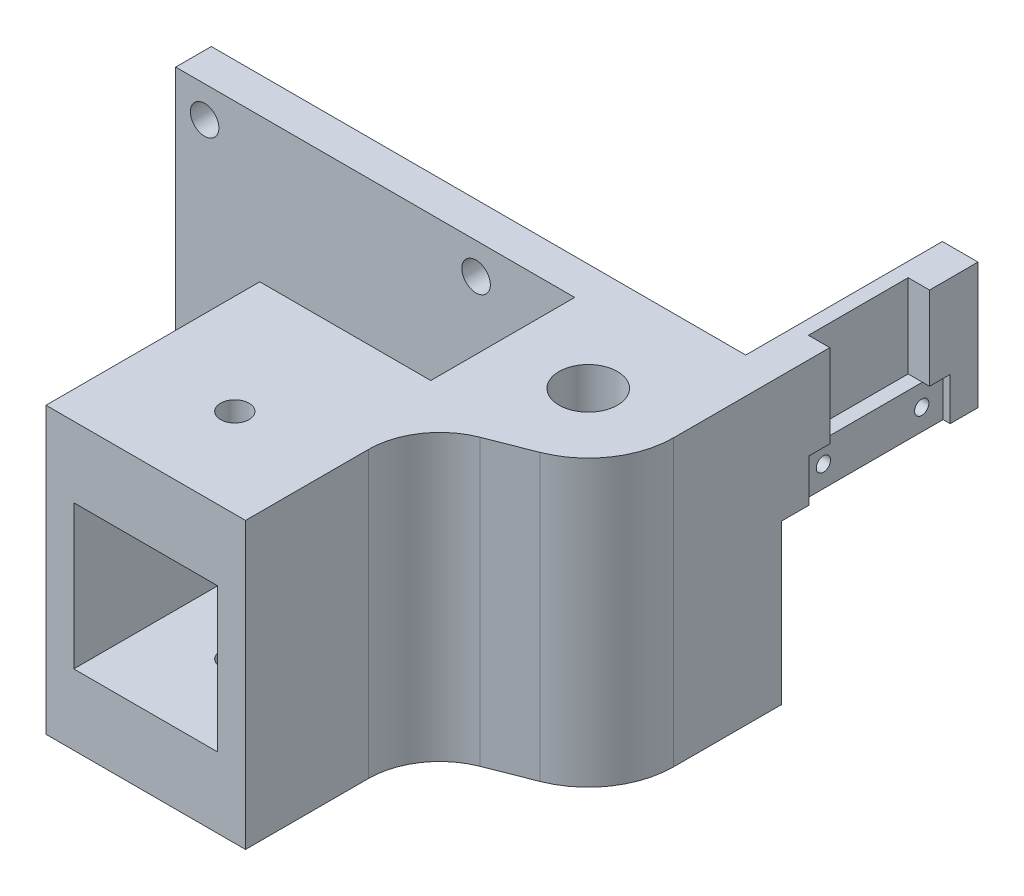
SolidWorks part; units mm, degrees
ref_plane "Front Plane" through (0, 0, 0) normal (0, 0, 1) x (1, 0, 0)
ref_plane "Top Plane" through (0, 0, 0) normal (0, 1, 0) x (1, 0, 0)
ref_plane "Right Plane" through (0, 0, 0) normal (1, 0, 0) x (0, 0, -1)
sketch "Sketch1" plane through (0, 0, 0) normal (0, 1, 0) x (1, 0, 0)
  line L0 (-32, 55.2) -> (-32, 50.2)
  line L1 (-32, 50.2) -> (24, 50.2)
  line L2 (24, 50.2) -> (24, 30)
  line L3 (24, 30) -> (0, 30)
  line L4 (0, 30) -> (0, 0)
  line L5 (0, 0) -> (28, 0)
  line L6 (28, 0) -> (28, 17.2586)
  line L7 (28, 55.2) -> (-32, 55.2)
  line L9 (40.3722, 28.9249) -> (34.3565, 26.5712)
  line L10 (28, 55.2) -> (43, 55.2)
  line L11 (43, 55.2) -> (43, 82.8)
  line L12 (43, 82.8) -> (48, 82.8)
  line L13 (48, 82.8) -> (48, 40.1)
  circle A1 centre (36, 40.1) radius 4.1
  arc A2 (48, 40.1) -> (40.3722, 28.9249) centre (36, 40.1) cw
  arc A3 (28, 17.2586) -> (34.3565, 26.5712) centre (38, 17.2586) cw
  point P8 (48, 51.7368)
  point P10 (47.3197, 55.2)
  point P11 (28, 12.7689)
  point P12 (48, 37.2626)
  point P18 (24, 40.1)
  point P19 (43.0102, 41.2257)
  point P22 (45.4925, 30.8582)
  point P23 (48, 30.8582)
  point P24 (0, 0)
  point P25 (28, 20.2156)
  point P26 (48, 34.6255)
  point P29 (38, 40.1)
  point P30 (37.365, 40.1)
  point P31 (0, 0)
  point P32 (28, 20.5347)
  point P33 (28, 24.0843)
  point P36 (43, 69)
  dimension "D6" = 8.2
  dimension "D7" = 5
  dimension "D10" = 10
  dimension "D1" = 5
  dimension "D2" = 4
  dimension "D3" = 30
  dimension "D4" = 20.2
  dimension "D5" = 28
  dimension "D8" = 8
  dimension "D9" = 19
  dimension "D11" = 13.8
extrude "Boss-Extrude1" add sketch "Sketch1" along normal blind 40 contours L6 A1 L9 | L6 L7 L0 L1 L2 L3 L4 L5 region at (-2, 0, -54.0487)
sketch "Sketch2" plane through (0, 0, 0) normal (0, 0, 1) x (1, 0, 0)
  line L0 (14, 30.1) -> (14, 9.9) construction
  line L1 (3.9, 30.1) -> (24.1, 30.1)
  line L2 (3.9, 30.1) -> (3.9, 9.9)
  line L3 (3.9, 9.9) -> (24.1, 9.9)
  line L4 (24.1, 30.1) -> (24.1, 9.9)
  line L5 (24.1, 20) -> (3.9, 20) construction
  line L8 (0, 40) -> (0, 0) construction
  line L9 (28, 40) -> (28, 0) construction
  line L10 (0, 40) -> (0, 0) construction
  line L11 (0, 40) -> (0, 0)
  point P10 (0, 20)
  dimension "D1" = 20.2
extrude "Cut-Extrude1" cut sketch "Sketch2" against normal blind 25 contours L4 L1 L2 L3 region at (14, 20, 0)
sketch "Sketch3" plane through (0, 40, 0) normal (0, 1, 0) x (1, 0, 0)
  line L1 (3.9, 25) -> (24.1, 25) construction
  line L2 (14, 25) -> (14, 0) construction
  line L4 (3.9, 25) -> (24.1, 25)
  line L5 (0, 0) -> (28, 0) construction
  circle A0 centre (14, 12.5) radius 2
  dimension "D1" = 4
extrude "Cut-Extrude2" cut sketch "Sketch3" against normal through all contours A0
fillet "Fillet1" radius 10 rebuild error yes
sketch "Sketch4" plane through (0, 0, -55.2) normal (0, 0, -1) x (-1, 0, 0)
  line L0 (32, 20) -> (-24.602, 20) construction
  line L1 (32, 40) -> (32, 0) construction
  line L2 (-24.602, 40) -> (-24.602, 0) construction
  line L3 (-24, 40) -> (-24, 0) construction
  line L4 (-24, 40) -> (-24, 0)
  circle A0 centre (-10.16, 35.62) radius 2
  circle A1 centre (27.94, 35.62) radius 2
  circle A3 centre (27.94, 4.38) radius 2
  circle A5 centre (-10.16, 4.38) radius 2
  dimension "D5" = 4
  dimension "D3" = 31.24
  dimension "D4" = 38.1
  dimension "D6" = 13.84
  dimension "D1" = 2
  dimension "D2" = 2
extrude "Cut-Extrude3" cut sketch "Sketch4" against normal up to surface (5 mm away) contours A5 | A1 | A3 | A0 up to face at (-4, 20, -50.2)
sketch "Sketch5" plane through (48, 0, 0) normal (1, 0, 0) x (0, 0, -1)
  line L0 (55.2, 40) -> (55.2, 0) construction
  line L1 (55.2, 40) -> (55.2, 0)
  line L2 (55.2, 20) -> (82.8, 20) construction
  line L4 (82.8, 40) -> (82.8, 0) construction
  line L6 (76, 22.3) -> (76, 44.3)
  line L7 (62, 22.3) -> (62, 44.3)
  line L8 (76, 44.3) -> (62, 44.3)
  line L9 (69, 26.3055) -> (69, 44.3) construction
  line L10 (75.9, 25.3) -> (62.1, 25.3) construction
  line L11 (59.1, 22.3) -> (59.1, 28.3)
  line L12 (59.1, 22.3) -> (78.9, 22.3)
  line L13 (59.1, 28.3) -> (78.9, 28.3)
  line L14 (78.9, 22.3) -> (78.9, 28.3)
  line L15 (78.9, 25.3) -> (59.1, 25.3) construction
  line L16 (76, 39.3) -> (104.946, 39.3)
  line L17 (55.2, 22.3) -> (87.8946, 22.3)
  circle A1 centre (69, 20) radius 1.5462
  circle A2 centre (75.9, 25.3) radius 1
  circle A3 centre (62.1, 25.3) radius 1
  point P15 (69, 44.3)
  point P16 (69, 20)
  point P28 (87.8946, 22.3)
  line M9 (40.1, 0) -> (82.8, 0)
  line M10 (82.8, 0) -> (82.8, 40)
  line M11 (82.8, 40) -> (40.1, 40)
  dimension "D1" = 2
  dimension "D2" = 13.8
  dimension "D3" = 5.3
  dimension "D4" = 19
  dimension "D5" = 3
  dimension "D6" = 3
  dimension "D7" = 5
  dimension "D8" = 14
extrude "Cut-Extrude4" cut sketch "Sketch5" against normal blind 1 contours A3 L7 L12 L6 A2 L13 | A3 L7 L13 L11 L12 | A2 L6 L12 L14 L13 region at (48, 25.3, -77.5416) region at (48, 25.3, -69) region at (48, 25.3, -60.4584)
extrude "Cut-Extrude5" cut sketch "Sketch5<5>" against normal blind 3 contours L7 L13 L6 M11 region at (48, 34.15, -69)
sketch "Sketch5<5>" plane through (48, 0, 0) normal (1, 0, 0) x (0, 0, -1) same geometry as "Sketch5"
extrude "Cut-Extrude6" cut sketch "Sketch5<6>" against normal blind 13 contours L17 L1 L12 A1 M9 M10 | A3 | A2 | A1 region at (48, 11.0407, -69)
sketch "Sketch5<6>" plane through (48, 0, 0) normal (1, 0, 0) x (0, 0, -1) same geometry as "Sketch5"
equation "\"local_angle\"=58.9479"
